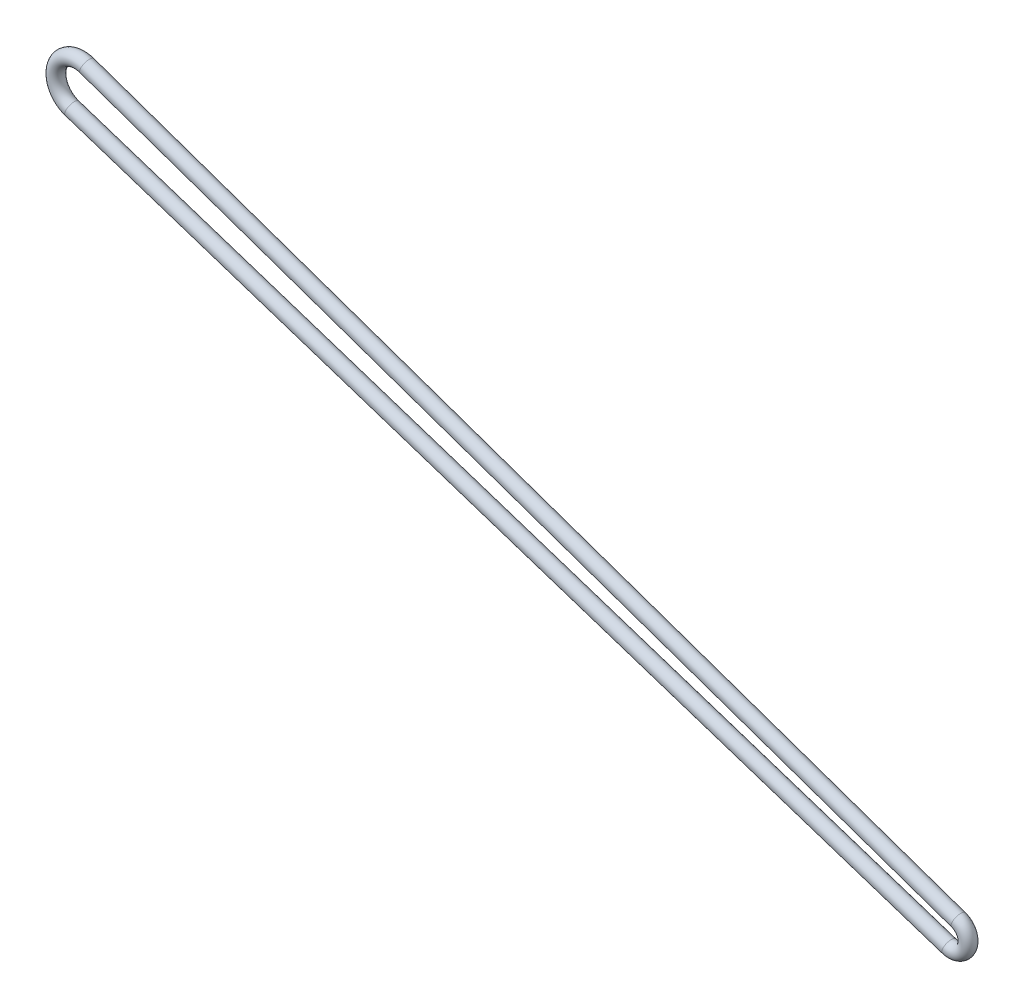
SolidWorks part; units mm, degrees
ref_plane "前视基准面" through (0, 0, 0) normal (0, 0, 1) x (1, 0, 0)
ref_plane "上视基准面" through (0, 0, 0) normal (0, 1, 0) x (1, 0, 0)
ref_plane "右视基准面" through (0, 0, 0) normal (1, 0, 0) x (0, 0, -1)
sketch "草图2" plane through (0, 0, 0) normal (0, 0, 1) x (1, 0, 0)
  line L0 (0, 0) -> (1, 0) construction
  line L1 (0, 0) -> (0, 1) construction
  line L2 (291.7354, 75.0379) -> (104.2714, 136.3929)
  line L3 (107.4731, 145.866) -> (293.7206, 80.9112)
  arc A0 (293.7206, 80.9112) -> (291.7354, 75.0379) centre (292.6997, 77.9841) cw
  arc A1 (104.2714, 136.3929) -> (107.4731, 145.866) centre (105.8266, 141.1449) cw
sweep "扫描19" add path "草图2" circular profile diameter 3 parameters "D3"=3
